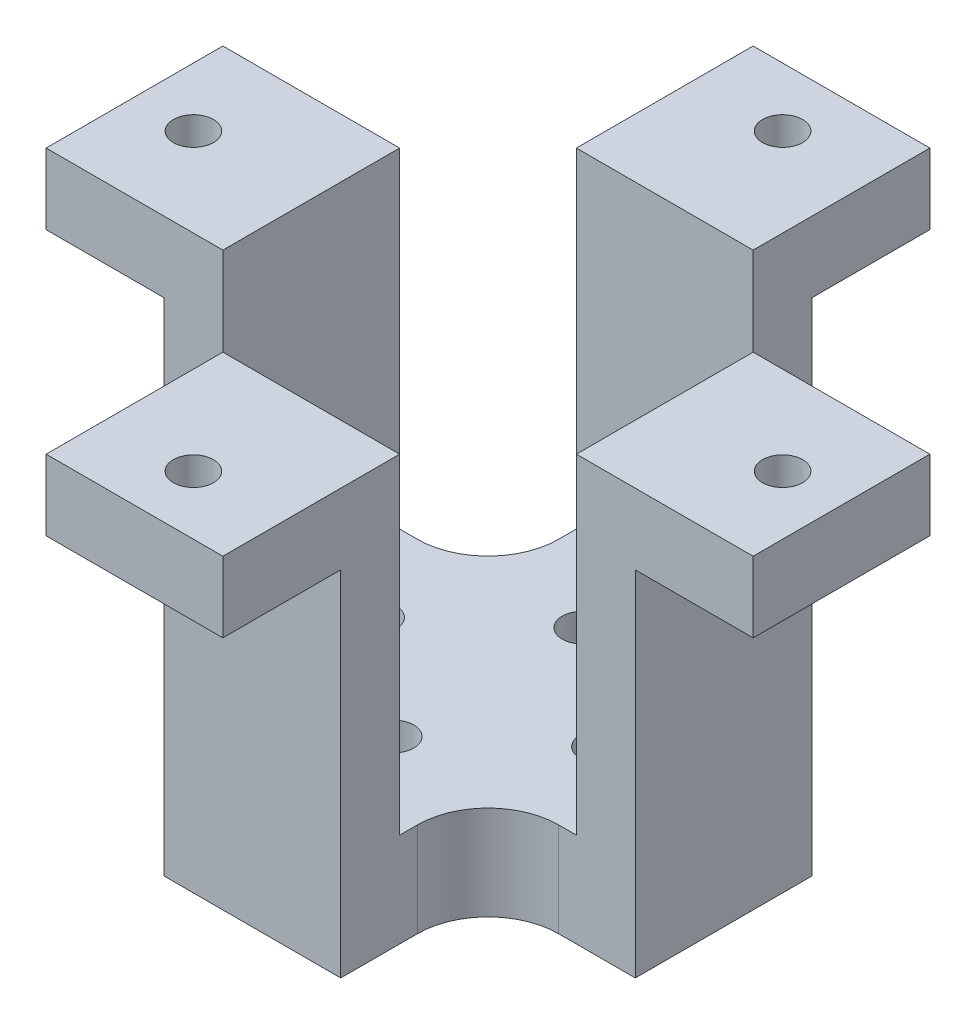
SolidWorks part; units mm, degrees
ref_plane "Front Plane" through (0, 0, 0) normal (0, 0, 1) x (1, 0, 0)
ref_plane "Top Plane" through (0, 0, 0) normal (0, 1, 0) x (1, 0, 0)
ref_plane "Right Plane" through (0, 0, 0) normal (1, 0, 0) x (0, 0, -1)
sketch "Sketch2" plane through (0, 0, 0) normal (0, 1, 0) x (1, 0, 0)
  line L1 (-7.5, 20) -> (7.5, 20)
  line L2 (-7.5, 20) -> (-7.5, 0)
  line L3 (-7.5, 0) -> (7.5, 0)
  line L4 (7.5, 20) -> (7.5, 0)
  point P4 (0, 0)
  dimension "D1" = 15
  dimension "D2" = 20
extrude "Boss-Extrude1" add sketch "Sketch2" against normal blind 8
sketch "Sketch3" plane through (0, 0, 0) normal (0, 1, 0) x (1, 0, 0)
  line L0 (7.5, 0) -> (7.5, 20) construction
  line L1 (-7.5, 20) -> (7.5, 20)
  line L2 (-7.5, 20) -> (-7.5, 15)
  line L3 (-7.5, 15) -> (7.5, 15)
  line L4 (7.5, 20) -> (7.5, 15)
  dimension "D1" = 5
extrude "Boss-Extrude4" add sketch "Sketch3" along normal blind 28
sketch "Sketch6" plane through (0, 28, 0) normal (0, 1, 0) x (1, 0, 0)
  line L1 (-7.5, 20) -> (7.5, 20)
  line L2 (-7.5, 20) -> (-7.5, 30)
  line L3 (-7.5, 30) -> (7.5, 30)
  line L4 (7.5, 20) -> (7.5, 30)
  dimension "D1" = 10
extrude "Boss-Extrude5" add sketch "Sketch6" against normal blind 6
sketch "Sketch8" plane through (0, 22, 0) normal (0, -1, 0) x (1, 0, 0)
  line L0 (7.5, -30) -> (-7.5, -30) construction
  line L1 (7.5, -20) -> (7.5, -30) construction
  circle A0 centre (0, -25) radius 1.7
  point P5 (0, -30)
  point P9 (7.5, -25)
  dimension "D1" = 3.4
extrude "Cut-Extrude1" cut sketch "Sketch8" against normal through all
ref_axis "Axis1" through (0, -8.4, 0) along (0, 1, 0)
pattern_circular "CirPattern1" count 4 over 360 about axis through (0, -8.4, 0) along (0, 1, 0) of "Boss-Extrude1", "Boss-Extrude4", "Boss-Extrude5", "Cut-Extrude1"
fillet "Fillet1" radius 6 4 edges at (7.5, -4, -7.5) (7.5, -4, 7.5) (-7.5, -4, 7.5) (-7.5, -4, -7.5)
sketch "Sketch9" plane through (0, -8, 0) normal (0, -1, 0) x (1, 0, 0)
  line L0 (0, 0) -> (0, 8) construction
  line L1 (0, 0) -> (9.5, 0) construction
  line L2 (0, 0) -> (0, -8) construction
  line L3 (0, 0) -> (-9.5, 0) construction
  circle A0 centre (0, 8) radius 1.7
  circle A1 centre (9.5, 0) radius 1.7
  circle A2 centre (0, -8) radius 1.7
  circle A3 centre (-9.5, 0) radius 1.7
  point P1 (0, 8)
  point P3 (9.5, 0)
  point P5 (0, -8)
  point P6 (-9.5, 0)
  dimension "D2" = 3.4
  dimension "D3" = 19
  dimension "D1" = 16
extrude "Cut-Extrude2" cut sketch "Sketch9" against normal through all
